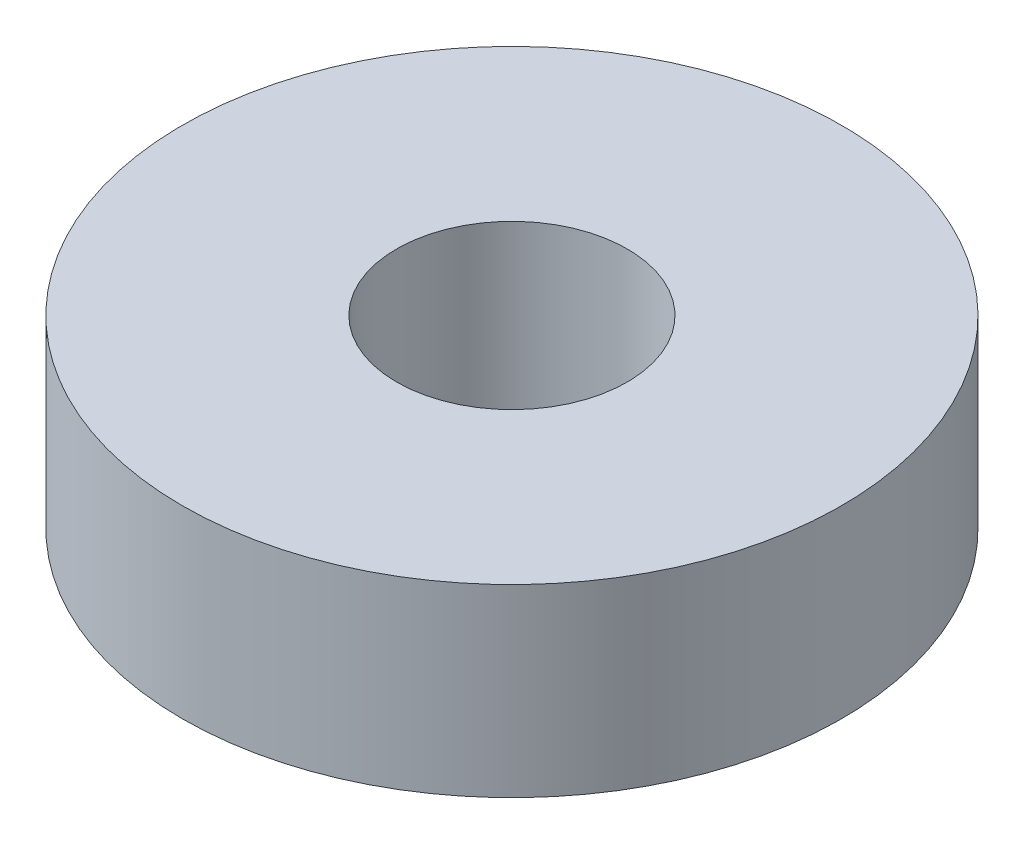
SolidWorks part; units mm, degrees
ref_plane "Front Plane" through (0, 0, 0) normal (0, 0, 1) x (1, 0, 0)
ref_plane "Top Plane" through (0, 0, 0) normal (0, 1, 0) x (1, 0, 0)
ref_plane "Right Plane" through (0, 0, 0) normal (1, 0, 0) x (0, 0, -1)
sketch "Sketch1" plane through (0, 0, 0) normal (0, 1, 0) x (1, 0, 0)
  circle A0 centre (0, 0) radius 50
  dimension "FLANGE_OD" = 100
extrude "Boss-Extrude1" add sketch "Sketch1" along normal blind 28
sketch "Sketch2" plane through (0, 0, 0) normal (0, 1, 0) x (1, 0, 0)
  circle A0 centre (0, 0) radius 17.5
  dimension "BORE_D" = 35
extrude "Cut-Extrude1" cut sketch "Sketch2" along normal through all
sketch "Sketch3" plane through (0, 28, 0) normal (0, 1, 0) x (1, 0, 0)
  circle A0 centre (0, 0) radius 10.9097 construction
  circle A1 centre (-10.9097, 0) radius 3.1559
  dimension "BOLT_D" = 6.3117
  dimension "BOLT_PCD" = 21.8195
extrude "Cut-Extrude2" cut sketch "Sketch3" against normal blind 22.8441 rebuild error yes
pattern_circular "CirPattern1" count 6 over 360 rebuild error yes
